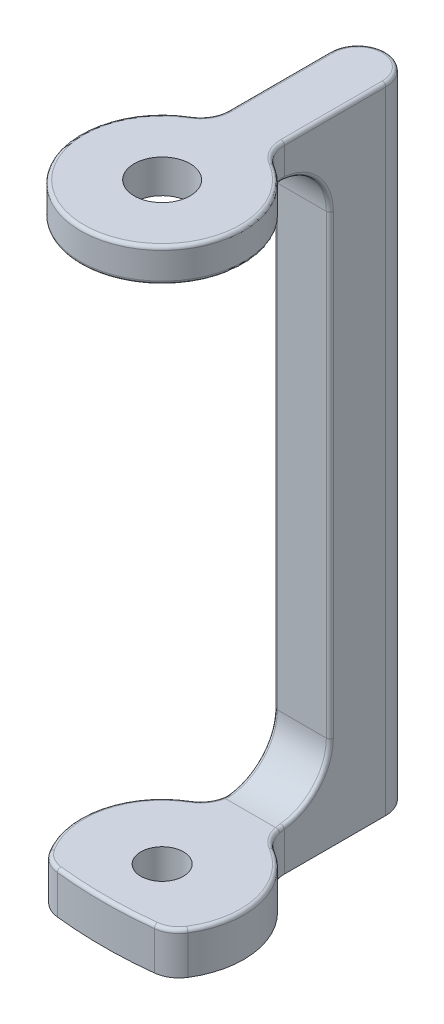
SolidWorks part; units mm, degrees
material "FormLabs Tough SLA- 3-D Printed"
ref_plane "Front Plane" through (0, 0, 0) normal (0, 0, 1) x (1, 0, 0)
ref_plane "Top Plane" through (0, 0, 0) normal (0, 1, 0) x (1, 0, 0)
ref_plane "Right Plane" through (0, 0, 0) normal (1, 0, 0) x (0, 0, -1)
sketch "Sketch1" plane through (0, 0, 0) normal (0, 1, 0) x (-1, 0, 0)
  line L0 (-3.175, 26.9875) -> (3.175, 26.9875) construction
  line L1 (3.175, 26.9875) -> (3.175, 17.4625)
  line L2 (3.175, 17.4625) -> (-3.175, 17.4625)
  line L3 (-3.175, 17.4625) -> (-3.175, 26.9875)
  line L4 (0, 42.8625) -> (0, 26.9875) construction
  line L5 (0, 0) -> (0, 17.4625) construction
  line L6 (0, 17.4625) -> (0, 26.9875) construction
  line L7 (-3.175, 26.9875) -> (-3.175, 34.1521)
  line L8 (3.175, 26.9875) -> (3.175, 34.1521)
  line L9 (0, 0) -> (-26.7541, 22.4494) construction
  line L10 (0, 0) -> (22.5912, 31.6601) construction
  line L11 (22.5912, 31.6601) -> (0, 42.8625) construction
  line L12 (0, 42.8625) -> (-26.7541, 22.4494) construction
  circle A0 centre (0, 42.8625) radius 2.413
  circle A2 centre (0, 0) radius 49.5681 construction
  circle A4 centre (-26.7541, 22.4494) radius 20.701 construction
  circle A5 centre (22.5912, 31.6601) radius 15.24 construction
  arc A6 (-6.868, 49.09) -> (-3.175, 34.1521) centre (0, 42.8625) ccw
  arc A7 (3.175, 34.1521) -> (6.868, 49.09) centre (0, 42.8625) ccw
  arc A8 (-6.868, 49.09) -> (6.868, 49.09) centre (0, 0) cw
  circle A9 centre (0, 42.8625) radius 9.271 construction
  dimension "D1" = 4.826
  dimension "D2" = 18.542
  dimension "D3" = 30.48
  dimension "D4" = 41.402
  dimension "D7" = 99.1362
  dimension "D12" = 42.8625
  dimension "D13" = 30.48
  dimension "D14" = 41.402
  dimension "D5" = 15.875
  dimension "D6" = 9.525
  dimension "D8" = 33.6523
  dimension "D9" = 25.2162
  dimension "D10" = 38.8937
  dimension "D11" = 34.925
  dimension "D15" = 6.35
extrude "Boss-Extrude1" add sketch "Sketch1" along normal blind 4.7625
sketch "Sketch2" plane through (0, 4.7625, 0) normal (0, 1, 0) x (1, 0, 0)
  line L1 (-3.175, -17.4625) -> (3.175, -17.4625)
  line L2 (-3.175, -17.4625) -> (-3.175, -26.9875)
  line L3 (-3.175, -26.9875) -> (3.175, -26.9875)
  line L4 (3.175, -17.4625) -> (3.175, -26.9875)
extrude "Boss-Extrude2" add sketch "Sketch2" along normal blind 63.5
sketch "Sketch3" plane through (0, 68.2625, 0) normal (0, 1, 0) x (1, 0, 0)
  line L0 (-3.175, -17.4625) -> (3.175, -17.4625)
  line L1 (3.175, -17.4625) -> (3.175, -34.1521)
  line L2 (-3.175, -17.4625) -> (-3.175, -34.1521)
  arc A0 (-3.175, -34.1521) -> (3.175, -34.1521) centre (0, -42.8625) ccw
  circle A1 centre (0, -42.8625) radius 3.175
  dimension "D1" = 6.35
extrude "Boss-Extrude3" add sketch "Sketch3" along normal blind 3.81
fillet "Fillet1" radius 5.842 2 edges at (0, 4.7625, 26.9875) (0, 68.2625, 26.9875)
fillet "Fillet2" radius 3.175 8 edges at (-3.175, 36.0362, 17.4625) (3.175, 36.0362, 17.4625) (3.175, 70.1675, 34.1521) (-3.175, 70.1675, 34.1521) (-3.175, 2.3813, 34.1521) (3.175, 2.3813, 34.1521) (6.868, 2.3813, 49.09) (-6.868, 2.3813, 49.09)
fillet "Fillet3" radius 0.3969 27 edges at (-3.7737, 68.2625, 34.0139) (-3.175, 66.3069, 28.4677) (-3.175, 36.5125, 26.9875) (-3.175, 6.7181, 28.4677) (-3.7737, 4.7625, 34.0139) (-9.0113, 4.7625, 40.6834) (-6.8506, 4.7625, 48.7938) (0, 4.7625, 49.5681) (6.8506, 4.7625, 48.7938) (9.0113, 4.7625, 40.6834) (3.7737, 4.7625, 34.0139) (3.175, 6.7181, 28.4677) (3.175, 36.5125, 26.9875) (3.175, 66.3069, 28.4677) (3.7737, 68.2625, 34.0139) (3.591, 72.0725, 33.7295) (0, 72.0725, 52.1335) (-3.591, 72.0725, 33.7295) (-3.175, 72.0725, 26.3979) (-2.2451, 72.0725, 18.3924) (2.2451, 72.0725, 18.3924) (0, 68.2625, 52.1335) (3.175, 72.0725, 26.3979)
